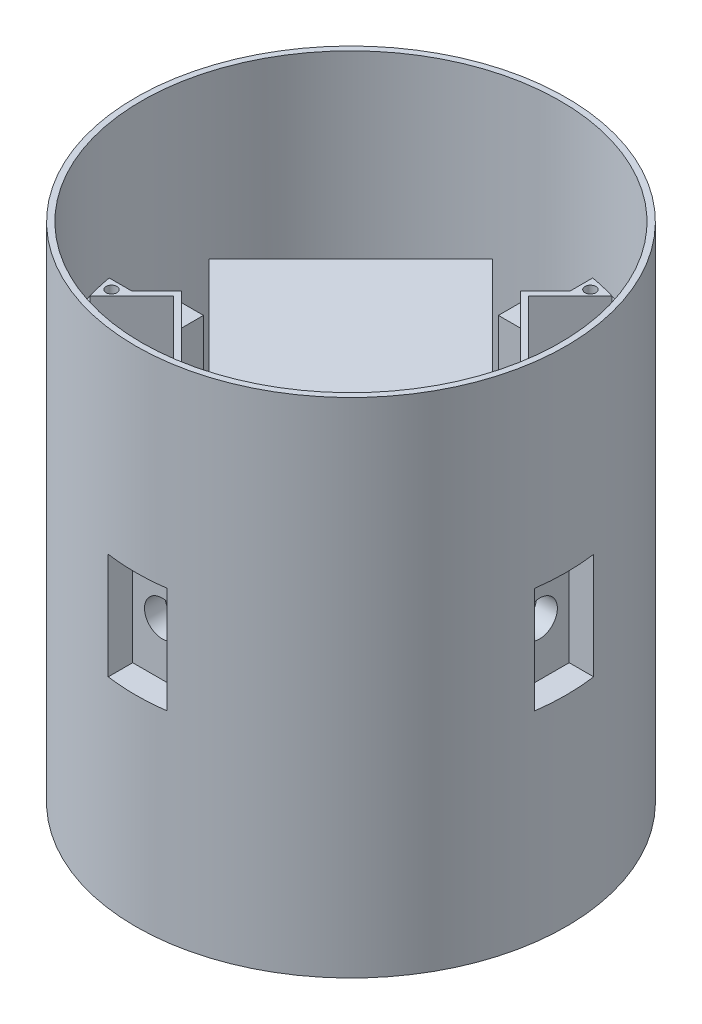
SolidWorks part; units mm, degrees
ref_plane "Front" through (0, 0, 0) normal (0, 0, 1) x (1, 0, 0)
ref_plane "Top" through (0, 0, 0) normal (0, 1, 0) x (1, 0, 0)
ref_plane "Right" through (0, 0, 0) normal (1, 0, 0) x (0, 0, -1)
sketch "草圖1" plane through (0, 0, 0) normal (0, 1, 0) x (1, 0, 0)
  line L0 (0, 78.355) -> (0, -92.3476) construction
  line L1 (-97.6496, 0) -> (95.3358, 0) construction
  line L21 (0, 48.0833) -> (-48.0833, 0)
  line L22 (-48.0833, 0) -> (0, -48.0833)
  line L23 (0, -48.0833) -> (48.0833, 0)
  line L24 (48.0833, 0) -> (0, 48.0833)
  line L26 (0, 0) -> (24.0416, 24.0416) construction
  circle A1 centre (0, 0) radius 71
  circle A2 centre (0, 0) radius 68 construction
  circle A4 centre (0, 0) radius 73
  circle A5 centre (0, 0) radius 67 construction
  circle A6 centre (42.4264, 0) radius 1.85
  circle A7 centre (0, -42.4264) radius 1.85
  circle A8 centre (-42.4264, 0) radius 1.85
  circle A9 centre (0, 42.4264) radius 1.85
  point P7 (0, 0)
  point P17 (0, 42.4264)
  point P19 (0, 0)
  point P23 (-73, 0)
  point P24 (-79.7794, 0)
  point P25 (-71, 0)
  point P26 (34, 0)
  point P27 (-34, 0)
  point P28 (-68, 0)
  point P31 (42.4264, 0)
  point P32 (0, -42.4264)
  point P33 (-42.4264, 0)
  point P34 (0, 0)
  point P44 (0, 0)
  dimension "D1" = 2
  dimension "D5" = 3.7
  dimension "D6" = 3
  dimension "D7" = 1
  dimension "D8" = 146
  dimension "D9" = 4
  dimension "D2" = 68
  dimension "D3" = 4
  dimension "D4" = 4
sketch "草圖3" plane through (0, 0, 0) normal (0, 0, 1) x (1, 0, 0)
  line L0 (0, 0) -> (0, 41.4301) construction
ref_plane "平面1" through (0, 0, 0) normal (-0.7071, 0, -0.7071) x (-0.7071, 0, 0.7071)
sketch "草圖4" plane through (0, 0, 0) normal (-0.7071, 0, -0.7071) x (-0.7071, 0, 0.7071)
  line L0 (-34, 0) -> (-34, 107.5)
  line L3 (34, 0) -> (34, 107.5)
  line L4 (34, 107.5) -> (-34, 107.5)
  line L5 (-34, 0) -> (34, 0)
  line L6 (-34, 15) -> (34, 15)
  line L7 (-34, 16.5) -> (34, 16.5)
  line L8 (-34, 31.5) -> (34, 31.5)
  line L9 (-34, 33) -> (34, 33)
  line L10 (-34, 48) -> (34, 48)
  line L11 (-34, 49.5) -> (34, 49.5)
  line L12 (-34, 64.5) -> (34, 64.5)
  line L13 (-34, 66) -> (34, 66)
  line L14 (-34, 82.5) -> (34, 82.5)
  line L15 (34, 82.5) -> (34, 81)
  line L16 (34, 81) -> (-34, 81)
  line L17 (-31.5, 31.5) -> (-31.5, 16.5)
  line L18 (-72.25, 0) -> (-72.25, 145.0993)
  line L19 (-68, 0) -> (-68, 146.8435)
  point P49 (-31.5, 16.5)
  point P52 (-31.5, 24)
  dimension "D1" = 1.5
  dimension "D2" = 15
  dimension "D3" = 1.5
  dimension "D4" = 1.5
  dimension "D5" = 1.5
  dimension "D6" = 15
  dimension "D7" = 15
  dimension "D8" = 15
  dimension "D9" = 15
  dimension "D10" = 1.5
  dimension "D11" = 25
  dimension "D12" = 58
  dimension "D19" = 107.5
extrude "填料-伸長1" add sketch "草圖4" along normal mid plane 68 contours L16 L3 L14 L0 | L13 L0 L12 L3 | L11 L0 L10 L3 | L9 L0 L8 L3 | L7 L0 L6 L3 region at (0, 15.75, 0) region at (0, 32.25, 0) region at (0, 48.75, 0) region at (0, 65.25, 0) region at (0, 81.75, 0)
extrude "填料-伸長2" add sketch "草圖1" along normal up to vertex (107.5 mm away) separate body contours A4 A1 region at (-72.7935, 0, 0) up to point (-24.0416, 107.5, 24.0416)
sketch "草圖5" plane through (0, 0, 0) normal (0, 0, 1) x (1, 0, 0)
  line L0 (0, 0) -> (0, 41.4301) construction
  line L7 (24.0416, 33) -> (-24.0416, 33) construction
  line L9 (-10, 53) -> (10, 53)
  line L10 (-10, 53) -> (-10, 13)
  line L11 (-10, 13) -> (10, 13)
  line L12 (10, 53) -> (10, 13)
  line L13 (-10, 53) -> (10, 13) construction
  line L14 (-10, 13) -> (10, 53) construction
  circle A0 centre (0, 33) radius 8
  circle A1 centre (0, 33) radius 6
  point P8 (0, 33)
  dimension "D1" = 16
  dimension "D2" = 20
  dimension "D4" = 12
  dimension "D3" = 40
sketch "草圖6" plane through (0, 0, 0) normal (0, 1, 0) x (1, 0, 0)
  line L0 (0, 78.355) -> (0, -92.3476) construction
  line L1 (-8.25, -57.0069) -> (8.25, -57.0069)
  line L2 (-8.25, -57.0069) -> (-8.25, -62.0069)
  line L3 (-8.25, -62.0069) -> (8.25, -62.0069)
  line L4 (8.25, -57.0069) -> (8.25, -62.0069)
  line L5 (-8.25, -57.0069) -> (8.25, -62.0069) construction
  line L6 (-8.25, -62.0069) -> (8.25, -57.0069) construction
  line L7 (-12, -62.0069) -> (12, -62.0069)
  line L8 (-12, -62.0069) -> (-12, -72.0069)
  line L9 (-12, -72.0069) -> (12, -72.0069)
  line L10 (12, -62.0069) -> (12, -72.0069)
  line L11 (-12, -62.0069) -> (12, -72.0069) construction
  line L12 (-12, -72.0069) -> (12, -62.0069) construction
  line L13 (6.7947, -72.0069) -> (-6.7947, -72.0069)
  line L14 (-5.5, -62.0069) -> (5.5, -62.0069)
  line L16 (-5.5, -72.0069) -> (5.5, -72.0069)
  line L17 (6.7947, -72.0069) -> (-6.7947, -72.0069)
  line L18 (6.7947, -72.0069) -> (6.7947, -57.0069)
  line L19 (6.7947, -57.0069) -> (-6.7947, -57.0069)
  line L20 (-6.7947, -72.0069) -> (-6.7947, -57.0069)
  line L21 (6.7947, -72.0069) -> (-6.7947, -57.0069) construction
  line L22 (6.7947, -57.0069) -> (-6.7947, -72.0069) construction
  circle A1 centre (0, -63.9107) radius 3.95
  circle A2 centre (0, -63.9107) radius 4.335 construction
  circle A3 centre (0, 0) radius 73 construction
  circle A5 centre (0, -63.9107) radius 5 construction
  point P0 (0, -59.5069)
  point P5 (0, -67.0069)
  point P24 (0, -64.5069)
  dimension "D5" = 7.9
  dimension "D7" = 10
  dimension "D6" = 8.67
  dimension "D1" = 24
  dimension "D2" = 10
  dimension "D3" = 16.5
  dimension "D4" = 5
extrude "填料-伸長4" add sketch "草圖6" along normal mid plane 40 from vertex contours L7 L10 L9 L8 starting at point (0, 33, 0)
extrude "填料-伸長5" add sketch "草圖5" against normal blind 5 from surface contours A0 starting at face at (0, 33, 62.0069)
pattern_circular "環狀複製排列1" count 4 over 360 about axis through (0, 107.5, 0) along (0, -1, 0) of "填料-伸長5", "填料-伸長4" reverse direction yes
shell "薄殼4" thickness 2 removed face at (0, 107.5, 73)
sketch "草圖8" plane through (-59.0069, 0, 0) normal (-1, 0, 0) x (0, 0, 1)
  circle A0 centre (0, 33) radius 6
  dimension "D1" = 12
extrude "除料-伸長7" cut sketch "草圖8" against normal up to next (2 mm away)
pattern_circular "環狀複製排列17" count 4 over 360 about axis through (0, 107.5, 0) along (0, -1, 0) of "除料-伸長7" reverse direction yes
extrude "填料-伸長6" add sketch "草圖1<43>" against normal blind 8 contours A4
sketch "草圖1<43>" plane through (0, 0, 0) normal (0, 1, 0) x (1, 0, 0) same geometry as "草圖1"
sketch "草圖9" plane through (0, 0, 0) normal (0, 1, 0) x (1, 0, 0)
  line L0 (36.7234, -36.7234) -> (8.696, -8.696) construction
  line L1 (36.7234, -57.9366) -> (15.5102, -36.7234)
  line L2 (36.7234, -57.9366) -> (57.9366, -36.7234)
  line L3 (57.9366, -36.7234) -> (36.7234, -15.5102)
  line L4 (15.5102, -36.7234) -> (36.7234, -15.5102)
  line L5 (36.7234, -57.9366) -> (36.7234, -15.5102) construction
  line L6 (57.9366, -36.7234) -> (15.5102, -36.7234) construction
  line L7 (36.7234, -36.7234) -> (47.33, -26.1168) construction
  line L8 (36.7234, -60.0579) -> (60.0579, -36.7234)
  line L9 (60.0579, -36.7234) -> (36.7234, -13.3889)
  line L10 (13.3889, -36.7234) -> (36.7234, -13.3889)
  line L11 (36.7234, -60.0579) -> (13.3889, -36.7234)
  line L13 (39.4256, -16.0911) -> (43.451, -12.0657)
  line L15 (43.451, -12.0657) -> (47.4764, -16.0911)
  line L18 (34.0212, -57.3557) -> (29.9958, -61.3811)
  line L19 (29.9958, -61.3811) -> (25.9705, -57.3557)
  line L20 (25.9705, -57.3557) -> (29.9958, -53.3304)
  line L24 (47.4764, -16.0911) -> (43.451, -20.1165)
  circle A4 centre (29.9777, -57.3739) radius 1.85
  circle A6 centre (43.4692, -16.0729) radius 1.85
  point P0 (36.7234, -36.7234)
  point P5 (36.7234, -36.7234)
  point P14 (0, 0)
  dimension "D3" = 1.5
  dimension "D1" = 30
  dimension "D2" = 30
sketch "草圖10" plane through (0, 0, 0) normal (0, 1, 0) x (1, 0, 0)
  line L0 (-97.6496, 0) -> (95.3358, 0) construction
  line L1 (58.9472, -17.6777) -> (16.5208, -60.1041)
  line L2 (58.9472, -17.6777) -> (-18.8345, 60.1041)
  line L3 (-18.8345, 60.1041) -> (-61.2609, 17.6777)
  line L4 (16.5208, -60.1041) -> (-61.2609, 17.6777)
  line L5 (58.9472, -17.6777) -> (-61.2609, 17.6777) construction
  line L6 (-18.8345, 60.1041) -> (16.5208, -60.1041) construction
  circle A0 centre (15.1794, -47.4336) radius 5
  point P4 (-1.1569, 0)
  point P9 (26.9537, -57.6134)
  dimension "D1" = 10
  dimension "D2" = 60
  dimension "D3" = 110
extrude "除料-伸長8" cut sketch "草圖10" against normal up to next (8 mm away) from surface contours A0 starting at face at (0, 0, 71)
sketch "草圖11" plane through (0, 0, 0) normal (0, 1, 0) x (1, 0, 0)
  line L0 (1.445, 58.0135) -> (-19.7682, 36.8003) construction
  line L1 (-26.9807, 58.1549) -> (-19.9096, 65.226)
  line L2 (-26.9807, 58.1549) -> (58.1549, -26.9807)
  line L3 (58.1549, -26.9807) -> (65.226, -19.9096)
  line L4 (-19.9096, 65.226) -> (65.226, -19.9096)
  line L5 (-26.9807, 58.1549) -> (65.226, -19.9096) construction
  line L6 (58.1549, -26.9807) -> (-19.9096, 65.226) construction
  line L7 (19.1227, 19.1227) -> (-4.1112, 42.3565) construction
  line L8 (24.0416, 24.0416) -> (-24.0416, -24.0416) construction
  line L9 (-18.8345, 60.1041) -> (-61.2609, 17.6777) construction
  line L10 (63.3168, -7.3939) -> (45.6392, -25.0715) construction
  line L12 (24.0416, 24.0416) -> (-24.0416, -24.0416) construction
  circle A0 centre (1.445, 58.0135) radius 1.5
  circle A1 centre (-19.7682, 36.8003) radius 1.5
  circle A4 centre (63.3168, -7.3939) radius 1.5
  circle A5 centre (45.6392, -25.0715) radius 1.5
  point P0 (19.1227, 19.1227)
  point P14 (-3.848, -13.335)
  point P17 (0, 0)
  point P18 (14.6053, 15.1622)
  point P20 (19.1227, 19.1227)
  dimension "D4" = 3
  dimension "D5" = 3
  dimension "D7" = 25
  dimension "D1" = 120.4
  dimension "D2" = 10
  dimension "D3" = 40
  dimension "D6" = 30
  dimension "D8" = 50
extrude "填料-伸長9" add sketch "草圖1<44>" along normal blind 10 from surface contours A4 A1 region at (-72.7935, 0, 0) starting at face at (0, 107.5, 71)
sketch "草圖1<44>" plane through (0, 0, 0) normal (0, 1, 0) x (1, 0, 0) same geometry as "草圖1"
extrude "填料-伸長10" add sketch "草圖1<45>" against normal blind 45 from surface contours A4 A1 region at (-72.7935, 0, 0) starting at face at (15.1794, -8, 52.4336)
sketch "草圖1<45>" plane through (0, 0, 0) normal (0, 1, 0) x (1, 0, 0) same geometry as "草圖1"
extrude "除料-伸長12" cut sketch "草圖1<46>" against normal blind 6 from surface contours A6 | A7 | A8 | A9 region at (42.4264, 0, 0) region at (0, 0, 42.4264) region at (-42.4264, 0, 0) region at (0, 0, -42.4264) starting at face at (15.1794, 0, 52.4336)
sketch "草圖1<46>" plane through (0, 0, 0) normal (0, 1, 0) x (1, 0, 0) same geometry as "草圖1"
sketch "草圖12" plane through (0, 0, 0) normal (0, 1, 0) x (1, 0, 0)
  line L0 (53.8108, 6.4346) -> (6.4346, 53.8108)
  line L1 (24.0416, 24.0416) -> (-24.0416, -24.0416) construction
  line L2 (54.5214, 54.5214) -> (-54.5214, -54.5214) construction
  line L3 (67.9529, 20.5768) -> (20.5768, 67.9529)
  line L4 (53.8108, 6.4346) -> (67.9529, 20.5768)
  line L5 (6.4346, 53.8108) -> (20.5768, 67.9529)
  line L6 (53.8108, 3.6062) -> (68.5807, 18.3762)
  line L7 (66.5099, 24.8482) -> (20.5768, 70.7813)
  line L8 (3.6062, 53.8108) -> (20.5768, 70.7813)
  line L9 (53.8108, 3.6062) -> (3.6062, 53.8108)
  line L10 (24.0416, 24.0416) -> (-24.0416, -24.0416) construction
  line L11 (12, 62.0069) -> (12, 75.9259)
  line L12 (53.8108, 3.6062) -> (70.7813, 20.5768) construction
  line L13 (70.7813, 20.5768) -> (20.5768, 70.7813) construction
  line L14 (62.0069, 12) -> (80.0977, 12)
  line L15 (30.1227, 30.1227) -> (37.6116, 37.6116) construction
  circle A0 centre (0, 0) radius 71 construction
  circle A1 centre (0, 0) radius 71
  circle A2 centre (15.0227, 66.1845) radius 1.85
  circle A3 centre (66.1845, 15.0227) radius 1.85
  circle A4 centre (15.0227, 66.1845) radius 2.2 construction
  point P4 (30.1227, 30.1227)
  dimension "D4" = 3.7
  dimension "D5" = 4.4
  dimension "D1" = 67
  dimension "D2" = 20
  dimension "D3" = 2
extrude "填料-伸長12" add sketch "草圖12" along normal blind 72 contours L6 A1 L4 L0 L5 L8 L9 | L3 A1 L7 | L14 A1 L6 | L8 A1 L11 | L8 A2 | A3 L6 | A3 L6 | L8 A2 region at (61.5316, 0, -12.8559) region at (44.9568, 0, -44.9568) region at (69.2548, 0, -15.1826) region at (17.4763, 0, -67.8231) region at (66.492, 0, -14.7151) region at (65.363, 0, -15.8442) region at (15.8442, 0, -65.363) region at (14.7151, 0, -66.492)
extrude "除料-伸長13" cut sketch "草圖12<5>" against normal blind 5 from surface contours L8 A2 | A2 | A3 region at (14.7151, 0, -66.492) starting at face at (36.254, 72, -36.254)
sketch "草圖12<5>" plane through (0, 0, 0) normal (0, 1, 0) x (1, 0, 0) same geometry as "草圖12"
pattern_circular "環狀複製排列20" count 2 over 360 about axis through (0, 107.5, 0) along (0, -1, 0) of "填料-伸長12", "除料-伸長13"
extrude "填料-伸長13" add sketch "草圖9" along normal blind 10 contours L11 L8 L9 L10 L1 L4 L3 L2 | L24 L15 L13 L9 A6 | L20 L19 L18 L11 A4 region at (35.839, 0, 58.2401) region at (31.928, 0, 59.2879) region at (41.5188, 0, 18.0233)
